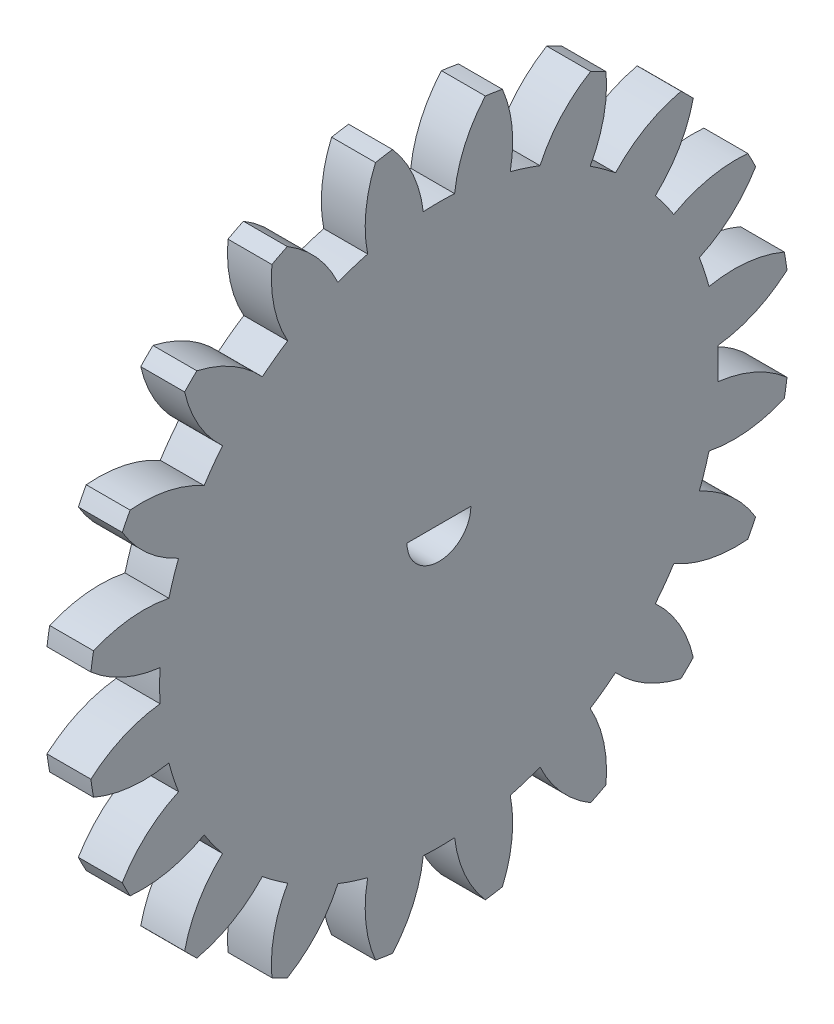
SolidWorks part; units mm, degrees
ref_plane "Plane1" through (0, 0, 0) normal (0, 0, 1) x (1, 0, 0)
ref_plane "Plane2" through (0, 0, 0) normal (0, 1, 0) x (1, 0, 0)
ref_plane "Plane3" through (0, 0, 0) normal (1, 0, 0) x (0, 0, -1)
sketch "HoldingSke" plane through (0, 0, 0) normal (0, 1, 0) x (1, 0, 0)
  line L0 (0, 0) -> (0.2349, -0.0855)
  line L1 (-15, 0) -> (100, 0) construction
  line L2 (0, 0) -> (-2.1039, 2.3779)
  line L3 (0, 0) -> (-11.863, 4.5341)
  line L4 (0, 0) -> (8.1152, 2.9537)
  line L5 (0, 0) -> (-46.8476, -17.4728)
  line L6 (0, 0) -> (-4.5593, -3.0762)
  line L7 (-2.1039, 2.3779) -> (8.6586, 51.2059)
  line L8 (-76.2, 54.61) -> (-76.1, 54.61)
  line L9 (-71.009, 38.7566) -> (-53.1078, 45.2721)
  line L10 (-76.2, 71.12) -> (104.1128, 71.12)
  line L11 (0, 0) -> (-5.5, 0)
  line L12 (-76.2, 101.6) -> (-76.073, 101.6)
  line L13 (24.9733, 27.94) -> (52.9518, 28.4284)
  line L14 (24.9733, 27.94) -> (24.9743, 27.94)
  line L15 (24.9733, 27.94) -> (100.4006, 29.5858)
  line L16 (-63.627, -4) -> (-12.827, -4)
  circle A0 centre (0, 0) radius 0.5
  circle A1 centre (0, 0) radius 34.999
  circle A2 centre (0, 0) radius 37.5
  circle A3 centre (0, 0) radius 0.5
  dimension "MHD" = 69.998
  dimension "Hub_dia" = 75
  dimension "Bore" = 1
  dimension "MBD" = 1
  dimension "Num_teeth" = 20
  dimension "Pitch" = 0.25
  dimension "Overall_len" = 50
  dimension "Show_teeth" = 20
  dimension "Thickness" = 5.5
  dimension "OAL" = 50.0001
  dimension "T_dim" = 0.1
  dimension "Ap" = 20
  dimension "H" = 19.05
  dimension "Pitch_radius" = 180.3128
  dimension "Width" = 5.5
  dimension "Backlash" = 0.127
  dimension "Addendum_fac" = 1
  dimension "Dedendum_fac" = 1.25
  dimension "Clearance_fac" = 0.25
  dimension "Dedendum_add" = 0.001
  dimension "Module" = 4
sketch "BasProSke" plane through (0, 0, 0) normal (0, 1, 0) x (1, 0, 0)
  line L0 (-10, 0) -> (60, 0) construction
  line L1 (0, 0) -> (0, 44)
  line L2 (0, 0) -> (5.5, 0)
  line L3 (5.5, 0) -> (5.5, 44)
  line L4 (5.5, 44) -> (0, 44)
  dimension "Thickness" = 5.5
  dimension "Diameter" = 88
revolve "Base-Revolve" add sketch "BasProSke" angle 360 about L0
sketch "TooCutSke" plane through (0, 0, 0) normal (1, 0, 0) x (0, 0, -1)
  line L1 (0, 0) -> (0, 107) construction
  line L2 (0, 0) -> (-3.3605, 39.8586) construction
  line L3 (0, 0) -> (-12.4815, 78.8048) construction
  line L4 (-3.3605, 39.8586) -> (-6.2407, 39.4024) construction
  arc A0 (1.9617, 34.944) -> (-1.9617, 34.944) centre (0, 0) ccw
  arc A1 (5.8321, 43.6374) -> (-5.8321, 43.6374) centre (0, 0) ccw
  circle A2 centre (0, 0) radius 40 construction
  circle A3 centre (0, 0) radius 37.5877 construction
  arc A4 (-1.9617, 34.944) -> (-5.8321, 43.6374) centre (-17.8525, 33.0775) ccw
  arc A5 (5.8321, 43.6374) -> (1.9617, 34.944) centre (17.8525, 33.0775) ccw
  dimension "Root_dia" = 69.998
  dimension "Overcut_dia" = 88.0508
  dimension "Pitch_dia" = 80
  dimension "Base_dia" = 75.1754
  dimension "Flank_rad" = 16
  dimension "Half_ang" = 9
  dimension "Half_CT" = 2.9161
extrude "ToothCut" cut sketch "TooCutSke" along normal through all
fillet "Breaks" [suppressed] radius 0.08 tangent propagation no
fillet "RootFillets" [suppressed] radius 1.001
pattern_circular "TeethCuts" count 20 every 18 about axis through (-10, 0, 0) along (1, 0, 0) of "ToothCut", "RootFillets", "Breaks"
sketch "HubNeaOneSke" plane through (0, 0, 0) normal (-1, 0, 0) x (0, 0, 1)
  circle A0 centre (0, 0) radius 34.999
  dimension "Diameter" = 69.998
extrude "HubNearOne" [suppressed] add sketch "HubNeaOneSke" along normal blind 44.5001
sketch "HubNeaBotSke" plane through (0, 0, 0) normal (-1, 0, 0) x (0, 0, 1)
  circle A0 centre (0, 0) radius 34.999
  dimension "Diameter" = 69.998
extrude "HubNearBoth" [suppressed] add sketch "HubNeaBotSke" along normal blind 22.25
ref_plane "FarPln" through (5.5, 0, 0) normal (1, 0, 0) x (0, 0, -1)
sketch "HubFarSke" plane through (5.5, 0, 0) normal (1, 0, 0) x (0, 0, -1)
  circle A0 centre (0, 0) radius 34.999
  dimension "Diameter" = 69.998
extrude "HubFar" [suppressed] add sketch "HubFarSke" along normal blind 22.25
sketch "BorSke" plane through (0, 0, 0) normal (1, 0, 0) x (0, 0, -1)
  circle A0 centre (0, 0) radius 0.5
  dimension "Diameter" = 1
extrude "Bore" cut sketch "BorSke" along normal mid plane 100.0001
sketch "KeySke" plane through (0, 0, 0) normal (1, 0, 0) x (0, 0, -1)
  line L0 (-0.05, 0) -> (-0.05, 0.6)
  line L1 (-0.05, 0.6) -> (0.05, 0.6)
  line L2 (0.05, 0.6) -> (0.05, 0)
  line L3 (0, 0) -> (0, 34) construction
  line L4 (-0.05, 0) -> (0.05, 0)
  dimension "Offset" = 0.6
  dimension "Width" = 0.1
extrude "Keyway" [suppressed] cut sketch "KeySke" along normal mid plane 100.0001
pattern_circular "Keyway2" [suppressed] count 2 every 90 about axis through (-10, 0, 0) along (1, 0, 0)
sketch "Croquis1" plane through (5.5, 0, 0) normal (1, 0, 0) x (0, 0, -1)
  line L0 (-4, 0) -> (4, 0)
  arc A0 (-4, 0) -> (4, 0) centre (0, 0) ccw
  dimension "D1" = 8
extrude "Cortar-Extruir1" cut sketch "Croquis1" against normal blind 5.5
sketch "Croquis2" plane through (5.5, 0, 0) normal (1, 0, 0) x (0, 0, -1)
  line L0 (-0.5, 0) -> (0.5, 0)
  arc A0 (0.5, 0) -> (-0.5, 0) centre (0, 0) ccw
extrude "Saliente-Extruir1" add sketch "Croquis2" against normal blind 5.5
equation "' \"Module@HoldingSke\" = 6.35"
equation "' \"Num_teeth@HoldingSke\" = 12"
equation "' \"Ap@HoldingSke\" =  20"
equation "' \"Ap@HoldingSke\" = 20"
equation "' \"Width@HoldingSke\" = 0.5 * 25.4"
equation "' \"Hub_dia@HoldingSke\"= 1 * 25.4"
equation "' \"Hub_dia@HoldingSke\" = 1 * 25.4"
equation "' \"Overall_len@HoldingSke\" = 1.0 * 25.4"
equation "' \"Bore@HoldingSke\" = 0.75 * 25.4"
equation "' \"T_dim@HoldingSke\" = 0.1 * 25.4"
equation "' \"Width@KeySke\" = 0.25 * 25.4"
equation "' \"Show_teeth@HoldingSke\" = 13"
equation "' \"Backlash@HoldingSke\" = 0.009 * 25.4"
equation "' \"Addendum_fac@HoldingSke\" = 1.0"
equation "' \"Dedendum_fac@HoldingSke\" = 1.25"
equation "' \"Dedendum_add@HoldingSke\" = 0.00005 * 25.4"
equation "' \"Clearance_fac@HoldingSke\" = 0.25"
equation "\"Pitch@HoldingSke\" = 1 / \"Module@HoldingSke\""
equation "\"Overcut_dia@TooCutSke\" = (\"Num_teeth@HoldingSke\" + 2 * \"Addendum_fac@HoldingSke\") / \"Pitch@HoldingSke\" + 0.002 * 25.4"
equation "\"Pitch_dia@TooCutSke\" = \"Num_teeth@HoldingSke\" / \"Pitch@HoldingSke\""
equation "\"Base_dia@TooCutSke\" = \"Num_teeth@HoldingSke\" / \"Pitch@HoldingSke\" * cos((\"Ap@HoldingSke\"  * 3.14159265 / 180))"
equation "\"Root_dia@TooCutSke\" = (\"Num_teeth@HoldingSke\" + 2) / \"Pitch@HoldingSke\" - 2 * (\"Addendum_fac@HoldingSke\" + \"Dedendum_fac@HoldingSke\") / \"Pitch@HoldingSke\" - \"Dedendum_add@HoldingSke\" * 2"
equation "\"Half_ang@TooCutSke\" = 180 / \"Num_teeth@HoldingSke\""
equation "\"Half_CT@TooCutSke\" = \"Num_teeth@HoldingSke\" / \"Pitch@HoldingSke\" * sin((3.14159265 / 2 / \"Num_teeth@HoldingSke\")) / 2 - 7 * \"Backlash@HoldingSke\" / 4"
equation "\"Flank_rad@TooCutSke\" = \"Num_teeth@HoldingSke\" / \"Pitch@HoldingSke\" / 5"
equation "\"Radius@RootFillets\" = \"Clearance_fac@HoldingSke\" / \"Pitch@HoldingSke\" + \"Dedendum_add@HoldingSke\""
equation "\"Break_rad@Breaks\" = 0.02 / \"Pitch@HoldingSke\""
equation "\"Thickness@HoldingSke\" = \"Width@HoldingSke\""
equation "\"OAL@HoldingSke\" = \"Thickness@HoldingSke\""
equation "\"MHD@HoldingSke\" = (\"Num_teeth@HoldingSke\" + 2) / \"Pitch@HoldingSke\" - 2 * (\"Addendum_fac@HoldingSke\" + \"Dedendum_fac@HoldingSke\")  / \"Pitch@HoldingSke\" - \"Dedendum_add@HoldingSke\" * 2"
equation "\"MBD@HoldingSke\" = (\"Num_teeth@HoldingSke\" + 2) / \"Pitch@HoldingSke\" - 2 * (\"Addendum_fac@HoldingSke\" + \"Dedendum_fac@HoldingSke\")  / \"Pitch@HoldingSke\" - \"Dedendum_add@HoldingSke\" * 2 - 0.002 * 25.4"
equation "\"MHD@HoldingSke\" = ((sgn( \"MHD@HoldingSke\" - \"Hub_dia@HoldingSke\" )-1)*( \"MHD@HoldingSke\" - \"Hub_dia@HoldingSke\" ))/-2+ \"Hub_dia@HoldingSke\""
equation "\"MBD@HoldingSke\" = ((sgn( \"MBD@HoldingSke\" - \"Bore@HoldingSke\" )-1)*( \"MBD@HoldingSke\" - \"Bore@HoldingSke\" ))/-2+ \"Bore@HoldingSke\""
equation "\"OAL@HoldingSke\" = ((sgn( \"OAL@HoldingSke\" - \"Overall_len@HoldingSke\" )+1)*( \"OAL@HoldingSke\" - \"Overall_len@HoldingSke\" ))/2 + \"Overall_len@HoldingSke\" + 0.000002 * 25.4"
equation "\"Num_teeth@TeethCuts\" = int( \"Show_teeth@HoldingSke\" ) + 1"
equation "\"Num_teeth@TeethCuts\" = ((sgn( \"Num_teeth@TeethCuts\" - \"Num_teeth@HoldingSke\" )-1)*( \"Num_teeth@TeethCuts\" - \"Num_teeth@HoldingSke\" ))/-2+ \"Num_teeth@HoldingSke\""
equation "\"Num_teeth@TeethCuts\" = ((sgn( \"Num_teeth@TeethCuts\" - 2.0)+1)*( \"Num_teeth@TeethCuts\" - 2.0))/2 +2.0"
equation "\"Angle@TeethCuts\" = 360.0 / \"Num_teeth@HoldingSke\""
equation "\"Diameter@BasProSke\" = (\"Num_teeth@HoldingSke\" + 2 * \"Addendum_fac@HoldingSke\") / \"Pitch@HoldingSke\""
equation "\"Thickness@BasProSke\"  = \"Thickness@HoldingSke\""
equation "' \"Fillet_rad@BasProSke\" =  \"Thickness@HoldingSke\" * 0.05"
equation "' \"Fillet_rad@BasProSke\" = \"Thickness@HoldingSke\" * 0.05"
equation "\"MHD@HoldingSke\" = ((sgn( \"MHD@HoldingSke\" - \"Root_dia@TooCutSke\" )-1)*( \"MHD@HoldingSke\" - \"Root_dia@TooCutSke\" ))/-2+ \"Root_dia@TooCutSke\""
equation "\"Diameter@HubNeaOneSke\" = \"MHD@HoldingSke\""
equation "\"Length@HubNearOne\" = \"OAL@HoldingSke\" - \"Thickness@BasProSke\""
equation "\"Diameter@HubNeaBotSke\" = \"MHD@HoldingSke\""
equation "\"Length@HubNearBoth\" = ( \"OAL@HoldingSke\" - \"Thickness@BasProSke\" ) / 2.0"
equation "\"Thickness@FarPln\" = \"Thickness@BasProSke\""
equation "\"Diameter@HubFarSke\" = \"MHD@HoldingSke\""
equation "\"Length@HubFar\" = ( \"OAL@HoldingSke\" - \"Thickness@BasProSke\" ) / 2.0"
equation "\"Diameter@BorSke\" = \"MBD@HoldingSke\""
equation "\"D1@Bore\" = \"OAL@HoldingSke\" * 2.0"
equation "\"D1@Keyway\" = \"OAL@HoldingSke\" * 2.0"
equation "\"Offset@KeySke\" = \"T_dim@HoldingSke\" + \"MBD@HoldingSke\" / 2.0"
